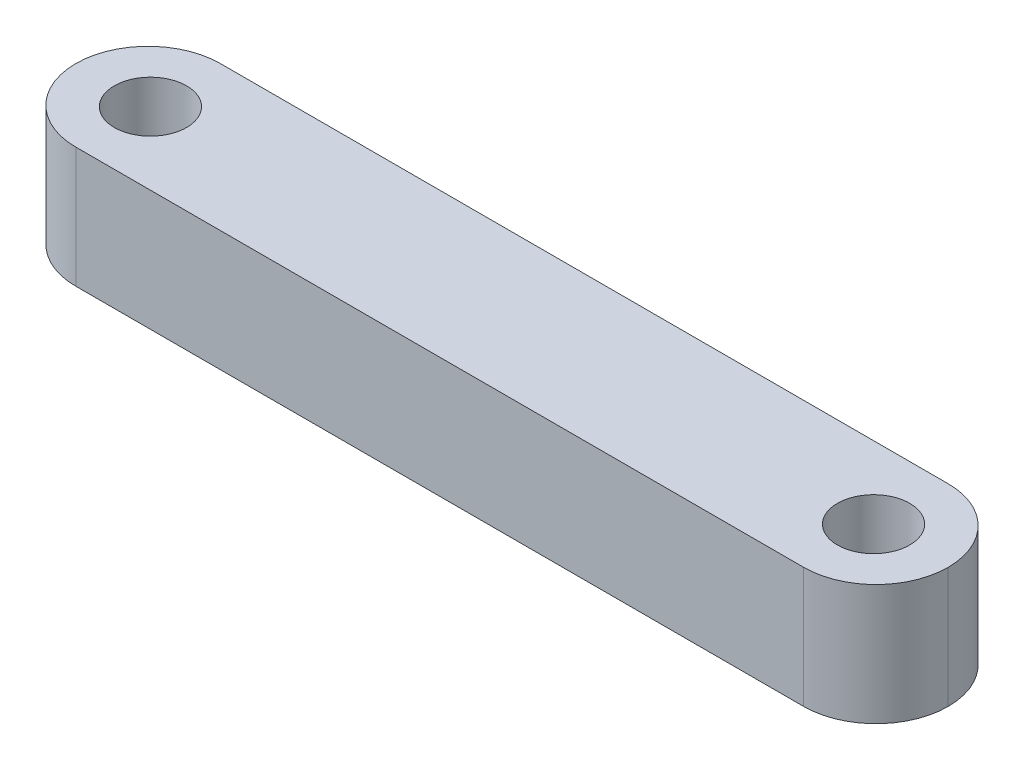
SolidWorks part; units mm, degrees
ref_plane "Front Plane" through (0, 0, 0) normal (0, 0, 1) x (1, 0, 0)
ref_plane "Top Plane" through (0, 0, 0) normal (0, 1, 0) x (1, 0, 0)
ref_plane "Right Plane" through (0, 0, 0) normal (1, 0, 0) x (0, 0, -1)
sketch "Sketch1" plane through (0, 0, 0) normal (0, 1, 0) x (1, 0, 0)
  line L0 (-30, 0) -> (30, 0) construction
  line L2 (-36.195, -6) -> (36.195, -6)
  line L3 (-36.195, -6) -> (-36.195, 6)
  line L4 (-36.195, 6) -> (36.195, 6)
  line L5 (36.195, -6) -> (36.195, 6)
  line L6 (-36.195, -6) -> (36.195, 6) construction
  line L7 (-36.195, 6) -> (36.195, -6) construction
  circle A0 centre (30, 0) radius 3
  circle A1 centre (-30, 0) radius 3
  point P4 (0, 0)
  point P7 (0, 0)
  dimension "D2" = 6
  dimension "D3" = 6
  dimension "D1" = 60
  dimension "D4" = 12
  dimension "D5" = 72.39
extrude "Boss-Extrude1" add sketch "Sketch1" along normal blind 10 contours A1 | A0 | L4 L5 L2 L3 region at (30, 0, 0) region at (-30, 0, 0)
fillet "Fillet1" radius 6 4 edges at (36.195, 5, -6) (36.195, 5, 6) (-36.195, 5, -6) (-36.195, 5, 6)
